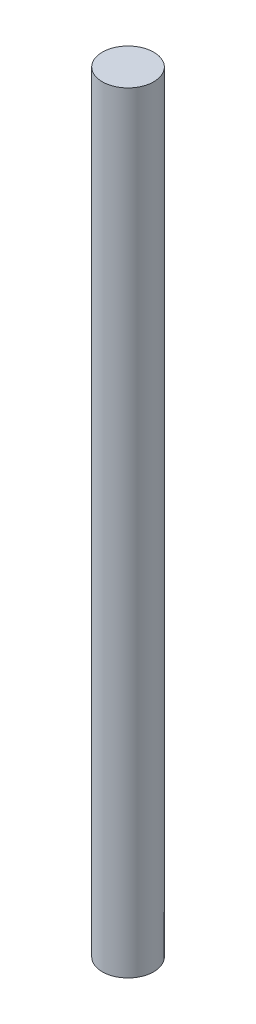
SolidWorks part; units mm, degrees
ref_plane "Plan de face" through (0, 0, 0) normal (0, 0, 1) x (1, 0, 0)
ref_plane "Plan de dessus" through (0, 0, 0) normal (0, 1, 0) x (1, 0, 0)
ref_plane "Plan de droite" through (0, 0, 0) normal (1, 0, 0) x (0, 0, -1)
sketch "Sketch1" plane through (0, 0, 0) normal (0, 1, 0) x (1, 0, 0)
  circle A0 centre (0, 0) radius 1.5
extrude "Boss-Extrude1" add sketch "Sketch1" along normal blind 45
